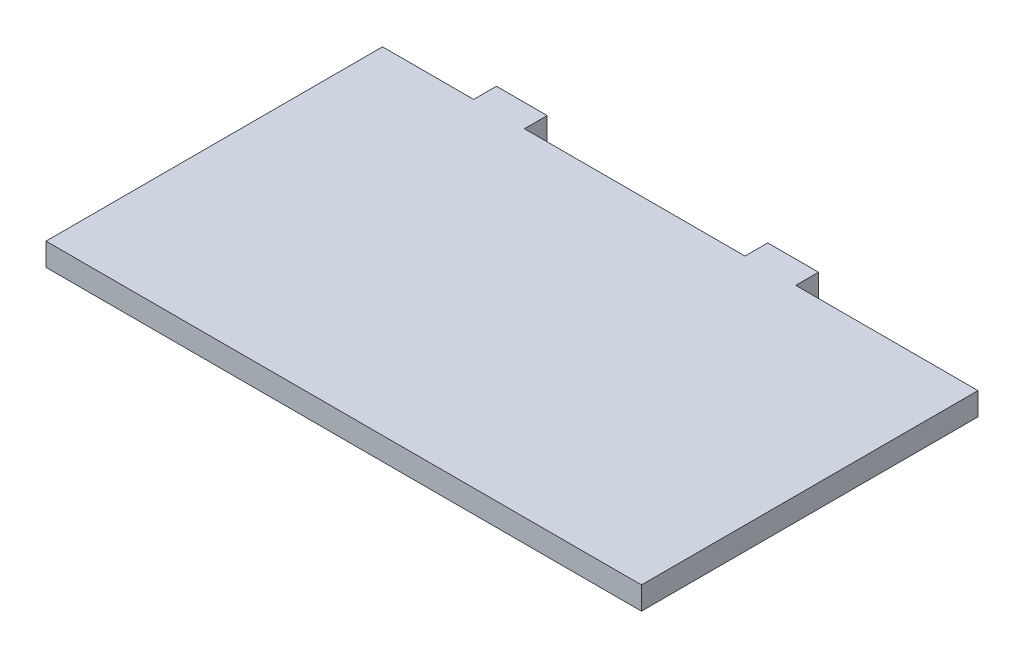
SolidWorks part; units mm, degrees
ref_plane "Front Plane" through (0, 0, 0) normal (0, 0, 1) x (1, 0, 0)
ref_plane "Top Plane" through (0, 0, 0) normal (0, 1, 0) x (1, 0, 0)
ref_plane "Right Plane" through (0, 0, 0) normal (1, 0, 0) x (0, 0, -1)
sketch "Sketch1" plane through (0, 0, 0) normal (0, 1, 0) x (1, 0, 0)
  line L1 (-73.025, -41.275) -> (73.025, -41.275)
  line L2 (-73.025, -41.275) -> (-73.025, 41.275)
  line L3 (-73.025, 41.275) -> (-50.673, 41.275)
  line L4 (73.025, -41.275) -> (73.025, 41.275)
  line L5 (-73.025, -41.275) -> (73.025, 41.275) construction
  line L6 (-73.025, 41.275) -> (73.025, -41.275) construction
  line L14 (-73.025, 0) -> (73.025, 0) construction
  line L15 (28.321, 46.863) -> (28.321, 41.275)
  line L16 (15.875, 46.863) -> (28.321, 46.863)
  line L17 (15.875, 41.275) -> (15.875, 46.863)
  line L18 (-38.227, 46.863) -> (-38.227, 41.275)
  line L19 (-50.673, 46.863) -> (-38.227, 46.863)
  line L20 (-50.673, 41.275) -> (-50.673, 46.863)
  line L21 (-38.227, 41.275) -> (15.875, 41.275)
  line L22 (28.321, 41.275) -> (73.025, 41.275)
  point P0 (0, 0)
  dimension "D1" = 146.05
  dimension "D2" = 82.55
  dimension "D3" = 12.446
  dimension "D4" = 5.588
  dimension "D5" = 88.9
  dimension "D6" = 22.352
extrude "Boss-Extrude1" add sketch "Sketch1" along normal blind 5.588
